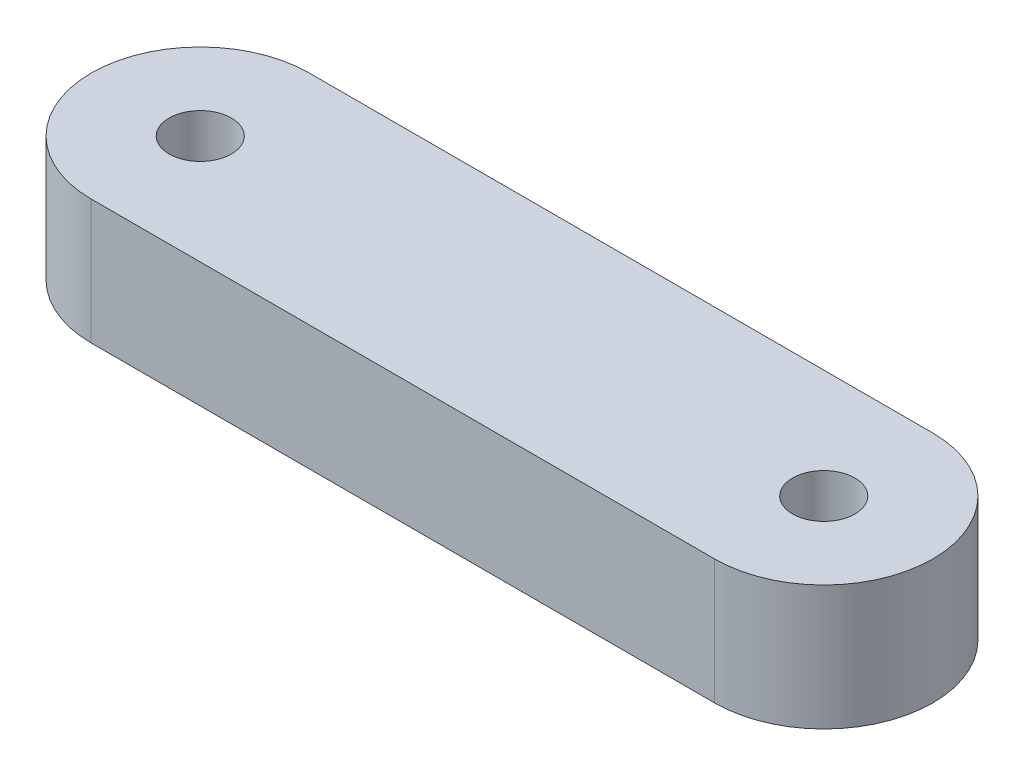
SolidWorks part; units mm, degrees
ref_plane "Front Plane" through (0, 0, 0) normal (0, 0, 1) x (1, 0, 0)
ref_plane "Top Plane" through (0, 0, 0) normal (0, 1, 0) x (1, 0, 0)
ref_plane "Right Plane" through (0, 0, 0) normal (1, 0, 0) x (0, 0, -1)
sketch "Sketch1" plane through (0, 0, 0) normal (0, 1, 0) x (1, 0, 0)
  line L0 (0, -8.7467) -> (-50, -8.7467)
  line L1 (0, 8.7467) -> (-50, 8.7467)
  circle A0 centre (0, 0) radius 2.5
  arc A1 (0, 8.7467) -> (0, -8.7467) centre (0, 0) cw
  circle A2 centre (-50, 0) radius 2.5
  arc A3 (-50, 8.7467) -> (-50, -8.7467) centre (-50, 0) ccw
  point P10 (0, 0)
  point P11 (0, 0)
  dimension "D1" = 5
  dimension "D2" = 50
extrude "Boss-Extrude1" add sketch "Sketch1" along normal blind 10
